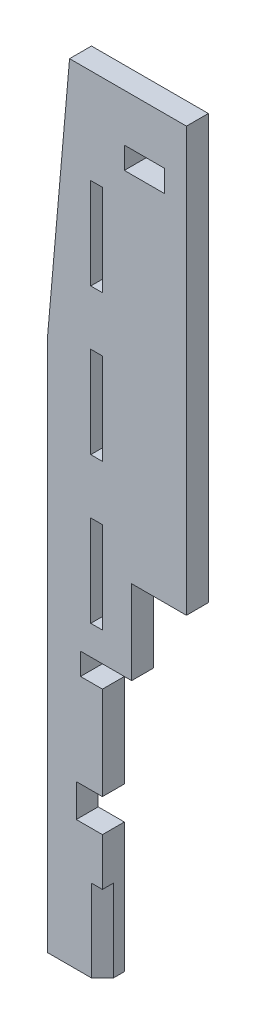
SolidWorks part; units mm, degrees
material "Plywood"
ref_plane "Plan de face" through (0, 0, 0) normal (0, 0, 1) x (1, 0, 0)
ref_plane "Plan de dessus" through (0, 0, 0) normal (0, 1, 0) x (1, 0, 0)
ref_plane "Plan de droite" through (0, 0, 0) normal (1, 0, 0) x (0, 0, -1)
sketch "Esquisse1" plane through (0, 0, 0) normal (0, 0, 1) x (1, 0, 0)
  line L0 (0, 0) -> (0, 215)
  line L1 (0, 215) -> (38, 215)
  line L2 (38, 215) -> (38, 0)
  line L3 (38, 0) -> (0, 0)
  dimension "D1" = 38
  dimension "D2" = 215
extrude "Boss.-Extru.1" add sketch "Esquisse1" along normal blind 6
sketch "Esquisse2" plane through (0, 0, 0) normal (0, 0, -1) x (-1, 0, 0)
  line L0 (-38, 0) -> (-38, 215) construction
  line L1 (-38, 76) -> (-23, 76)
  line L2 (-38, 76) -> (-38, 99)
  line L3 (-38, 99) -> (-23, 99)
  line L4 (-23, 76) -> (-23, 99)
  line L5 (0, 0) -> (-38, 0) construction
  dimension "D1" = 15
  dimension "D2" = 76
  dimension "D3" = 23
extrude "Enlèv. mat.-Extru.1" cut sketch "Esquisse2" against normal through all
sketch "Esquisse3" plane through (0, 0, 6) normal (0, 0, 1) x (1, 0, 0)
  line L1 (38, 0) -> (18, 0)
  line L2 (38, 0) -> (38, 22.5)
  line L3 (38, 22.5) -> (18, 22.5)
  line L4 (18, 0) -> (18, 22.5)
  dimension "D1" = 20
  dimension "D2" = 22.5
extrude "Enlèv. mat.-Extru.2" cut sketch "Esquisse3" against normal blind 7.5
chamfer "Chanfrein1" distance 6 angle 45 1 edges at (18, 11.25, 6)
sketch "Esquisse5" plane through (0, 0, 0) normal (0, 0, -1) x (-1, 0, 0)
  line L1 (-15, 44.5) -> (-7.8413, 44.5)
  line L2 (-15, 44.5) -> (-15, 35.5)
  line L3 (-15, 35.5) -> (-7.8413, 35.5)
  line L4 (-7.8413, 44.5) -> (-7.8413, 35.5)
  line L6 (-30, 35.5) -> (-38, 35.5) construction
  line L7 (-18, 0) -> (-18, 22.5) construction
  point P6 (0, 0)
  dimension "D1" = 7.1587
  dimension "D2" = 9
  dimension "D3" = 3
extrude "Enlèv. mat.-Extru.4" cut sketch "Esquisse5" against normal through all
sketch "Esquisse6" plane through (0, 0, 0) normal (0, -1, 0) x (-1, 0, 0)
  line L0 (0, -6) -> (-12, -6) construction
  line L1 (0, -6) -> (0, 0) construction
  circle A0 centre (-5.5, -3) radius 2.5
  dimension "D3" = 5
  dimension "D1" = 3
  dimension "D2" = 5.5
extrude "Enlèv. mat.-Extru.5" cut sketch "Esquisse6" against normal blind 10
sketch "Esquisse7" plane through (0, 0, 6) normal (0, 0, 1) x (1, 0, 0)
  line L0 (15, 196) -> (15, 76) construction
  line L1 (15, 84) -> (11.8, 84)
  line L2 (15, 84) -> (15, 109)
  line L3 (15, 109) -> (11.8, 109)
  line L4 (11.8, 84) -> (11.8, 109)
  line L6 (11.8, 124) -> (15, 124)
  line L7 (11.8, 124) -> (11.8, 149)
  line L8 (11.8, 149) -> (15, 149)
  line L9 (15, 124) -> (15, 149)
  line L10 (15, 164) -> (11.8, 164)
  line L11 (15, 164) -> (15, 189)
  line L12 (15, 189) -> (11.8, 189)
  line L13 (11.8, 164) -> (11.8, 189)
  line L14 (38, 215) -> (0, 215) construction
  dimension "D1" = 3.2
  dimension "D2" = 26
  dimension "D3" = 25
  dimension "D4" = 25
  dimension "D5" = 25
  dimension "D6" = 15
  dimension "D7" = 15
extrude "Enlèv. mat.-Extru.6" cut sketch "Esquisse7" against normal blind 10
sketch "Esquisse9" plane through (0, 0, 0) normal (0, 0, -1) x (-1, 0, 0)
  line L0 (0, 0) -> (-18, 0) construction
  line L1 (-38, 76) -> (-15, 76)
  line L2 (-38, 76) -> (-38, 0)
  line L3 (-38, 0) -> (-15, 0)
  line L4 (-15, 76) -> (-15, 0)
  line L5 (-15, 44.5) -> (-15, 35.5) construction
extrude "Enlèv. mat.-Extru.7" cut sketch "Esquisse9" against normal blind 10
sketch "Esquisse10" plane through (0, 0, 0) normal (0, 0, -1) x (-1, 0, 0)
  line L1 (-15, 76) -> (-9, 76)
  line L2 (-15, 76) -> (-15, 70)
  line L3 (-15, 70) -> (-9, 70)
  line L4 (-9, 76) -> (-9, 70)
extrude "Enlèv. mat.-Extru.8" cut sketch "Esquisse10" against normal blind 10
sketch "Esquisse11" plane through (0, 0, 6) normal (0, 0, 1) x (1, 0, 0)
  line L0 (15, 202) -> (21, 202) construction
  line L1 (21, 202) -> (32, 202)
  line L2 (21, 202) -> (21, 196)
  line L3 (21, 196) -> (32, 196)
  line L4 (32, 202) -> (32, 196)
  line L5 (40.5, 196) -> (15, 196) construction
  line L6 (21, 196) -> (21, 202) construction
  line L7 (32, 196) -> (32, 202) construction
  dimension "D1" = 0
  dimension "D2" = 0
  dimension "D3" = 0
  dimension "D4" = 0
extrude "Enlèv. mat.-Extru.9" cut sketch "Esquisse11" against normal blind 10
chamfer "Chanfrein2" distance 6 angle 85 1 edges at (0, 215, 3) first distance on face at (19, 215, 3)
